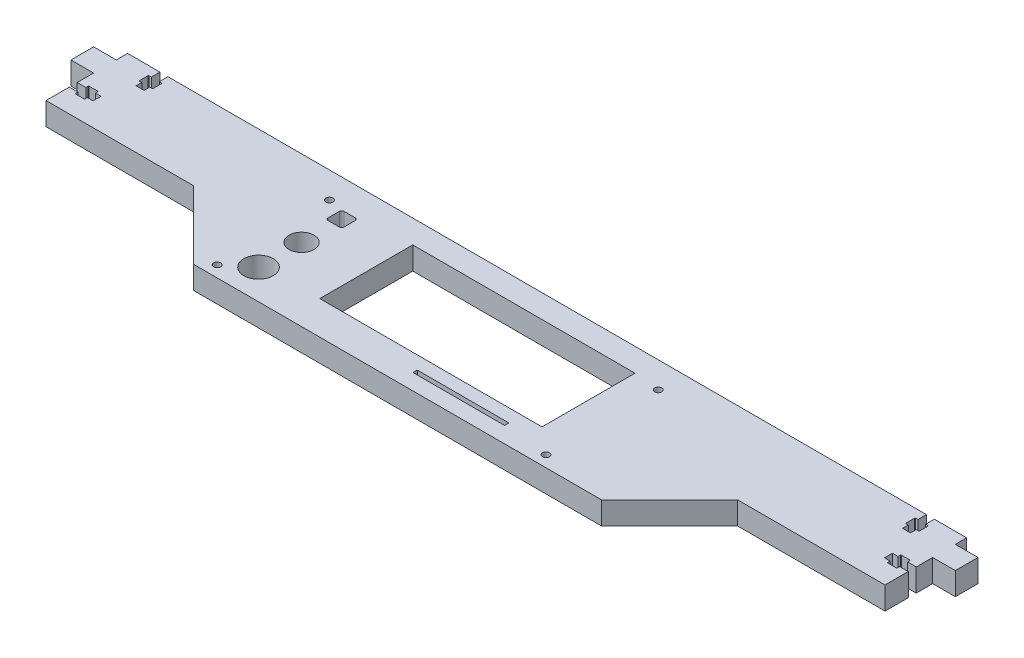
SolidWorks part; units mm, degrees
ref_plane "Front Plane" through (0, 0, 0) normal (0, 0, 1) x (1, 0, 0)
ref_plane "Top Plane" through (0, 0, 0) normal (0, 1, 0) x (1, 0, 0)
ref_plane "Right Plane" through (0, 0, 0) normal (1, 0, 0) x (0, 0, -1)
sketch "Sketch1" plane through (0, 0, 0) normal (0, 1, 0) x (1, 0, 0)
  line L0 (0, 18) -> (0, -18) construction
  line L1 (-185, 18) -> (0, 18)
  line L2 (-185, 18) -> (-185, 13)
  line L3 (-185, -18) -> (0, -18)
  line L4 (0, 18) -> (0, -18)
  line L5 (-185, 18) -> (0, 0) construction
  line L6 (-185, -18) -> (0, 0) construction
  line L7 (-185, 13) -> (-195, 13)
  line L8 (-195, 13) -> (-195, 3)
  line L9 (-195, 3) -> (-185, 3)
  line L10 (-185, 3) -> (-185, -18)
  point P0 (0, 0)
  dimension "D6" = 10
  dimension "D7" = 10
  dimension "D1" = 185
  dimension "D2" = 36
  dimension "D4" = 5
  dimension "D9" = 18
extrude "MainShape" add sketch "Sketch1" along normal blind 10 contours L2 L7 L8 L9 region at (-93.9423, 0, -0.1183)
sketch "Sketch2" plane through (0, 10, 0) normal (0, 1, 0) x (1, 0, 0)
  line L0 (-169, 18) -> (-169, 7.5) construction
  line L1 (-185, 18) -> (0, 18) construction
  line L2 (-170.75, 18) -> (-170.75, 14.2)
  line L3 (-170.75, 14.2) -> (-171.75, 14.2)
  line L4 (-172, 13.95) -> (-172, 10.25)
  line L5 (-171.75, 10) -> (-170.75, 10)
  line L6 (-170.75, 10) -> (-170.75, 7.5)
  line L7 (-170.75, 7.5) -> (-167.25, 7.5)
  line L8 (-185, 18) -> (-185, 13) construction
  line L9 (-170.75, 18) -> (-167.25, 18)
  line L10 (-167.25, 10) -> (-167.25, 7.5)
  line L11 (-166.25, 10) -> (-167.25, 10)
  line L12 (-166, 13.95) -> (-166, 10.25)
  line L13 (-167.25, 14.2) -> (-166.25, 14.2)
  line L14 (-167.25, 18) -> (-167.25, 14.2)
  line L16 (-185, -6) -> (-174.5, -6) construction
  line L50 (-185, 3) -> (-185, -18) construction
  line L51 (-174.5, -7.75) -> (-174.5, -4.25)
  line L52 (-174.5, -4.25) -> (-177, -4.25)
  line L53 (-177, -4.25) -> (-177, -3.25)
  line L54 (-177.25, -3) -> (-180.95, -3)
  line L55 (-181.2, -3.25) -> (-181.2, -4.25)
  line L56 (-181.2, -4.25) -> (-185, -4.25)
  line L57 (-185, -4.25) -> (-185, -7.75)
  line L58 (-195, 13) -> (-195, 3) construction
  line L59 (-181.2, -7.75) -> (-185, -7.75)
  line L60 (-181.2, -8.75) -> (-181.2, -7.75)
  line L61 (-177.25, -9) -> (-180.95, -9)
  line L62 (-177, -7.75) -> (-177, -8.75)
  line L63 (-174.5, -7.75) -> (-177, -7.75)
  arc A0 (-172, 10.25) -> (-171.75, 10) centre (-171.75, 10.25) ccw
  arc A1 (-171.75, 14.2) -> (-172, 13.95) centre (-171.75, 13.95) ccw
  arc A2 (-166.25, 14.2) -> (-166, 13.95) centre (-166.25, 13.95) cw
  arc A3 (-166, 10.25) -> (-166.25, 10) centre (-166.25, 10.25) cw
  arc A16 (-177, -3.25) -> (-177.25, -3) centre (-177.25, -3.25) ccw
  arc A17 (-180.95, -3) -> (-181.2, -3.25) centre (-180.95, -3.25) ccw
  arc A18 (-180.95, -9) -> (-181.2, -8.75) centre (-180.95, -8.75) cw
  arc A19 (-177, -8.75) -> (-177.25, -9) centre (-177.25, -8.75) cw
  point P14 (-172, 10)
  point P17 (-172, 14.2)
  point P28 (-166, 14.2)
  point P29 (-166, 10)
  point P34 (-195, 8)
  point P45 (-177, -3)
  point P48 (-181.2, -3)
  dimension "D8" = 0.25
  dimension "D16" = 0.25
  dimension "D1" = 10.5
  dimension "D2" = 1.75
  dimension "D3" = 1.75
  dimension "D4" = 8
  dimension "D5" = 3
  dimension "D6" = 4.2
  dimension "D7" = 16
  dimension "D9" = 10.5
  dimension "D10" = 8
  dimension "D11" = 4.2
  dimension "D12" = 3
  dimension "D13" = 1.75
  dimension "D14" = 1.75
  dimension "D15" = 14
extrude "ScrewSlots" cut sketch "Sketch2" against normal through all
mirror "Mirror1" about plane through (0, 0, 0) normal (1, 0, 0) of "ScrewSlots", "MainShape"
sketch "Sketch6" plane through (0, 10, 0) normal (0, 1, 0) x (1, 0, 0)
  line L0 (0, -18) -> (0, -48) construction
  line L2 (-185, -18) -> (185, -18) construction
  line L3 (90, -48) -> (-90, -48)
  line L4 (-90, -48) -> (-120, -18)
  line L5 (90, -48) -> (120, -18)
  line L6 (-120, -18) -> (120, -18)
  dimension "D1" = 135
  dimension "D2" = 30
  dimension "D3" = 90
extrude "Boss-Extrude1" add sketch "Sketch6" against normal through all
sketch "Sketch8" plane through (0, 10, 0) normal (0, 1, 0) x (1, 0, 0)
  line L0 (-71.5, 4.8833) -> (-77.5, 4.8833) construction
  line L1 (-77, -1.6167) -> (-72, -1.6167)
  line L2 (-78, -0.6167) -> (-78, 4.3833)
  line L3 (-77, 5.3833) -> (-72, 5.3833)
  line L4 (-71, -0.6167) -> (-71, 4.3833)
  line L5 (-78, -1.6167) -> (-71, 5.3833) construction
  line L6 (-78, 5.3833) -> (-71, -1.6167) construction
  line L7 (-71.5, -1.1167) -> (-71.5, 4.8833) construction
  circle A0 centre (-74.5, -34.7667) radius 6.5
  circle A1 centre (-74.5, -15.8167) radius 5.5
  arc A2 (-77, -1.6167) -> (-78, -0.6167) centre (-77, -0.6167) cw
  circle A3 centre (-74.5, -34.7667) radius 6 construction
  circle A4 centre (-74.5, -15.8167) radius 3.5 construction
  arc A5 (-72, -1.6167) -> (-71, -0.6167) centre (-72, -0.6167) ccw
  arc A6 (-72, 5.3833) -> (-71, 4.3833) centre (-72, 4.3833) cw
  arc A7 (-78, 4.3833) -> (-77, 5.3833) centre (-77, 4.3833) cw
  point P6 (-74.5, 1.8833)
  dimension "D1" = 0.5
  dimension "D2" = 2
  dimension "D3" = 0.5
  dimension "D5" = 1
  dimension "D4" = 0.5
extrude "Cut-Extrude2" cut sketch "Sketch8" against normal through all
sketch "Sketch7" plane through (0, 10, 0) normal (0, 1, 0) x (1, 0, 0)
  circle A0 centre (60.5, -43.0167) radius 1.55
  circle A1 centre (-84.5, -43.0167) radius 1.55
  circle A2 centre (-84.5, 6.4833) radius 1.55
  circle A3 centre (60.5, 6.4833) radius 1.55
  dimension "D1" = 3.1
  dimension "D2" = 3.1
  dimension "D3" = 3.1
  dimension "D4" = 3.1
extrude "Cut-Extrude1" cut sketch "Sketch7" against normal through all
sketch "Sketch9" plane through (0, 10, 0) normal (0, 1, 0) x (1, 0, 0)
  line L0 (0, 7.2333) -> (0, -32.7667) construction
  line L1 (48.5, 7.2333) -> (-48.5, 7.2333) construction
  line L2 (-48.5, -32.7667) -> (48.5, -32.7667) construction
  line L3 (-48.5, -12.7667) -> (48.5, -12.7667) construction
  line L4 (-48.5, 7.2333) -> (-48.5, -32.7667) construction
  line L5 (48.5, -32.7667) -> (48.5, 7.2333) construction
  line L7 (-49, -33.2667) -> (49, -33.2667)
  line L8 (-49, -33.2667) -> (-49, 7.7333)
  line L9 (-49, 7.7333) -> (49, 7.7333)
  line L10 (49, -33.2667) -> (49, 7.7333)
  line L11 (-49, -33.2667) -> (49, 7.7333) construction
  line L12 (-49, 7.7333) -> (49, -33.2667) construction
  point P12 (0, -12.7667)
  dimension "D1" = 0.5
  dimension "D2" = 0.5
extrude "Cut-Extrude3" cut sketch "Sketch9" against normal through all and the other way through all
sketch "Sketch10" plane through (0, 10, 0) normal (0, 1, 0) x (1, 0, 0)
  line L0 (20, -39.2667) -> (20, -40.7667) construction
  line L1 (40, -39.2667) -> (0, -39.2667) construction
  line L2 (0, -40.7667) -> (40, -40.7667) construction
  line L3 (0, -40.0167) -> (40, -40.0167) construction
  line L4 (0, -39.2667) -> (0, -40.7667) construction
  line L5 (40, -40.7667) -> (40, -39.2667) construction
  line L7 (-0.2, -40.9667) -> (40.2, -40.9667)
  line L8 (-0.2, -40.9667) -> (-0.2, -39.0667)
  line L9 (-0.2, -39.0667) -> (40.2, -39.0667)
  line L10 (40.2, -40.9667) -> (40.2, -39.0667)
  line L11 (-0.2, -40.9667) -> (40.2, -39.0667) construction
  line L12 (-0.2, -39.0667) -> (40.2, -40.9667) construction
  point P12 (20, -40.0167)
  dimension "D1" = 0.2
  dimension "D2" = 0.2
extrude "Cut-Extrude4" cut sketch "Sketch10" against normal through all
sketch "Sketch11" [suppressed] plane through (0, 0, 0) normal (0, -1, 0) x (1, 0, 0)
  line L1 (-149.5, -2.5) -> (-167.5, -2.5)
  line L2 (-147.5, -0.5) -> (-147.5, 6.5)
  line L3 (-149.5, 8.5) -> (-167.5, 8.5)
  line L4 (-169.5, -0.5) -> (-169.5, 6.5)
  line L5 (-147.5, -2.5) -> (-169.5, 8.5) construction
  line L6 (-147.5, 8.5) -> (-169.5, -2.5) construction
  line L7 (170.75, -7.5) -> (167.25, -7.5) construction
  line L8 (-174.5, 7.75) -> (-174.5, 4.25) construction
  arc A0 (-147.5, 6.5) -> (-149.5, 8.5) centre (-149.5, 6.5) ccw
  arc A1 (-167.5, 8.5) -> (-169.5, 6.5) centre (-167.5, 6.5) ccw
  arc A2 (-167.5, -2.5) -> (-169.5, -0.5) centre (-167.5, -0.5) cw
  arc A3 (-149.5, -2.5) -> (-147.5, -0.5) centre (-149.5, -0.5) ccw
  point P0 (-158.5, 3)
  dimension "D3" = 2
  dimension "D1" = 22
  dimension "D2" = 11
  dimension "D4" = 5
  dimension "D5" = 5
extrude "LCDCableCutout" [suppressed] cut sketch "Sketch11" against normal through all
equation "\"Y-ROD-SPACING\"=75"
equation "\"Y-BED-OFFSET\"=2"
equation "\"Y-BED-ROD-INSET\"=3.5"
equation "\"T-SLOT-NUT-FILLET-RADIUS\"=0.25"
equation "\"T-SLOT-SCREW-SHAFT-RADIUS\"=1.75"
equation "\"T-SLOT-SCREW-SHAFT-CUTOUT-LENGTH\"=10.5"
equation "\"T-SLOT-NUT-DEPTH\"=4.2"
equation "\"T-SLOT-NUT-WIDTH\"=3"
equation "\"T-SLOT-NUT-END-DISTANCE\"=8"
equation "\"ACRYLIC-TAB-CUTOUT-SIZE\"=\"ACRYLIC-THICKNESS\"+\"ACRYLIC-TAB-TOLERANCE\"*2"
equation "\"ACRYLIC-M3-HOLE\"=3.1"
equation "\"SMOOTHROD-CAP-SCREW-DISTANCE\"=20"
equation "\"D2@Sketch2\"=\"T-SLOT-SCREW-SHAFT-RADIUS\""
equation "\"D1@Sketch2\"=\"T-SLOT-SCREW-SHAFT-CUTOUT-LENGTH\""
equation "\"D6@Sketch2\"=\"T-SLOT-NUT-DEPTH\""
equation "\"D5@Sketch2\"=\"T-SLOT-NUT-WIDTH\""
equation "\"D3@Sketch2\"=\"T-SLOT-SCREW-SHAFT-RADIUS\""
equation "\"D8@Sketch2\"=\"T-SLOT-NUT-FILLET-RADIUS\""
equation "\"D4@Sketch2\"=\"T-SLOT-NUT-END-DISTANCE\""
equation "\"D11@Sketch2\"=\"T-SLOT-NUT-DEPTH\""
equation "\"D10@Sketch2\"=\"T-SLOT-NUT-END-DISTANCE\""
equation "\"D13@Sketch2\"=\"T-SLOT-SCREW-SHAFT-RADIUS\""
equation "\"D14@Sketch2\"=\"T-SLOT-SCREW-SHAFT-RADIUS\""
equation "\"D16@Sketch2\"=\"T-SLOT-NUT-FILLET-RADIUS\""
equation "\"D9@Sketch2\"=\"T-SLOT-SCREW-SHAFT-CUTOUT-LENGTH\""
equation "\"ACRYLIC-TAB-WIDTH\"=\"ACRYLIC-THICKNESS\""
equation "\"D6@Sketch1\"=\"ACRYLIC-TAB-WIDTH\""
equation "\"D7@Sketch1\"=\"ACRYLIC-TAB-WIDTH\""
equation "\"FRAME-WIDTH-INNER\"=370"
equation "\"D1@Sketch1\"=\"FRAME-WIDTH-INNER\"/2"
equation "\"X-ROD-SPACING\"=45"
equation "\"Z-ROD-SPACING\"=17.5"
equation "\"ACRYLIC-THICKNESS\"=10"
equation "\"ACRYLIC-THICKNESS2\"=4.5"
equation "\"NEMA17-HOLE-SPACING\"=31"
equation "\"NEMA17-CENTRAL-CUTOUT\"=22.5"
equation "\"Z-BRACKET-REACH\"=55"
equation "\"TOP-BRACKET-SPACING\"=40"
equation "\"SMOOTHROD-X-LENGTH\"=350"
equation "\"SMOOTHROD-Y-LENGTH\"=350"
equation "\"SMOOTHROD-Z-LENGTH\"=350"
equation "\"SMOOTHROD-TIGHTENING-HEADROOM\"=.25"
equation "\"LEADSCREW-Z-LENGTH\"=300"
equation "\"SCREW-LENGTH-FRAME\"=\"ACRYLIC-THICKNESS\" + 10"
equation "\"SCREW-HEAD-RADIUS\"=6"
equation "\"PRINTED-X-SMOOTHROD-DIAMETER\"=8.2"
equation "\"PRINTED-X-SMOOTHROD-CUTOUT\"=10"
equation "\"PRINTED-X-BASE-HEIGHT\"=10"
equation "\"PRINTED-LM8UU-CUTOUT-SIZE\"=15.25"
equation "\"PRINTED-LM8UU-CUTOUT-LENGTH\"=24.5"
equation "\"PRINTED-X-IDLER-HEIGHT\"=16"
equation "\"PSU-MOUNTING-WIDTH\"=95"
equation "\"PSU-MOUNTING-HEIGHT\"=177"
equation "\"D1@MainShape\"=\"ACRYLIC-THICKNESS\""
equation "\"Y-BELT-TO-ROD-DISTANCE\"=20"
equation "\"SPOOL-HOLDER-ROD-SPACING\"=150"
equation "\"Z-ROD-INSET\"=16"
equation "\"D7@Sketch2\"=\"Z-ROD-INSET\""
equation "\"D1@Sketch7\"=\"ACRYLIC-M3-HOLE\""
equation "\"D2@Sketch7\"=\"ACRYLIC-M3-HOLE\""
equation "\"D3@Sketch7\"=\"ACRYLIC-M3-HOLE\""
equation "\"D4@Sketch7\"=\"ACRYLIC-M3-HOLE\""
equation "\"Y-BED-SCREW-SPACING\"=209"
equation "\"Y-BED-SCREW-CUTOUT-SLOT-HEIGHT\"=2"
equation "\"ACRYLIC-TAB-TOLERANCE\"=.1"
equation "\"SCREW-LENGTH-MOTOR\"=\"ACRYLIC-THICKNESS\" + 5"
equation "\"SCREW-LENGTH-EXTRUDER\"=28"
equation "\"PRINTED-M3-HOLE\"=3.5"
equation "\"PRINTED-M3-NUT-AF\"=6.25"
equation "\"ACRYLIC-X-CARRIAGE-WIDTH\"=55"
equation "\"ACRYLIC-X-CARRIAGE-HEIGHT\"=75"
equation "\"ACRYLIC-X-CARRIAGE-LM8UU-CUTOUT-WIDTH\"=24.25"
equation "\"ACRYLIC-X-CARRIAGE-LM8UU-CUTOUT-HEIGHT\"=11.5"
equation "\"ACRYLIC-X-CARRIAGE-SCREW-SPACING-X\"=15"
equation "\"ACRYLIC-X-CARRIAGE-SCREW-SPACING-Y\"=33"
equation "\"ACRYLIC-X-CARRIAGE-CENTER-TAB-SPACING\"=14"
equation "\"ACRYLIC-X-CARRIAGE-EXTRUDER-OFFSET\"=26"
equation "\"ACRYLIC-X-CARRIAGE-EXTRUDER-ANGLE\"=90"
equation "\"ACRYLIC-X-CARRIAGE-EXTRUDER-SHELF-DEPTH\"=\"ACRYLIC-X-CARRIAGE-EXTRUDER-OFFSET\" + 28"
equation "\"ACRYLIC-X-CARRIAGE-EXTRUDER-BRACE-SPACING\"=23"
equation "\"ACRYLIC-X-CARRIAGE-EXTRUDER-BRACE-TAB-OFFSET\"=20"
equation "\"ACRYLIC-X-CARRIAGE-EXTRUDER-BRACE-HEIGHT\"=35"
equation "\"ACRYLIC-X-CARRIAGE-EXTRUDER-BRACE-SCREW-SPACING\"=22"
equation "\"ACRYLIC-X-CARRIAGE-DUAL-WIDTH-MULTIPLIER\"=1.65"
equation "\"ACRYLIC-X-CARRIAGE-DUAL-HOTEND-SPACING\"=42"
equation "\"ACRYLIC-X-CARRIAGE-DUAL-WIDTH\"=95"
equation "\"ACRYLIC-X-CARRIAGE-DUAL-HOTEND-SEPARATION\"=35"
equation "\"ACRYLIC-X-CARRIAGE-DUAL-MOUNT-PLATE-DEPTH\"=75"
equation "\"ACRYLIC-X-CARRIAGE-DUAL-MOUNT-BRACE-WIDTH\"=33"
equation "\"ACRYLIC-X-CARRIAGE-DUAL-MOUNT-SCREW-WIDTH\"=40"
equation "\"BLOWER-FAN-WIDTH\"=15"
